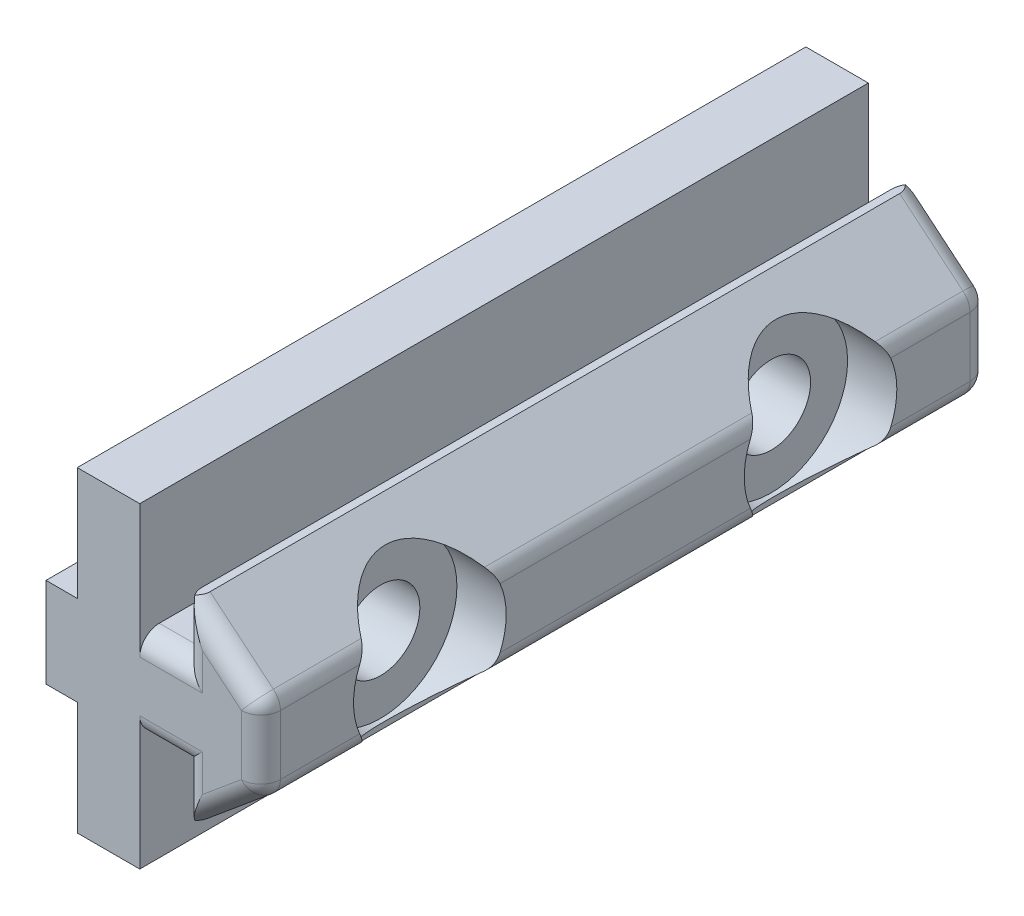
SolidWorks part; units mm, degrees
ref_plane "Front Plane" through (0, 0, 0) normal (0, 0, 1) x (1, 0, 0)
ref_plane "Top Plane" through (0, 0, 0) normal (0, 1, 0) x (1, 0, 0)
ref_plane "Right Plane" through (0, 0, 0) normal (1, 0, 0) x (0, 0, -1)
ref_plane "Plane1" through (0, 0, 23.6855) normal (0, 0, 1) x (1, 0, 0)
sketch "Sketch1" plane through (0, 0, 23.6855) normal (0, 0, 1) x (1, 0, 0)
  line L0 (3.302, 6.35) -> (-4.064, 6.35)
  line L1 (-4.064, 6.35) -> (-4.064, -6.35)
  line L2 (-4.064, -6.35) -> (3.302, -6.35)
  line L3 (3.302, -6.35) -> (7.874, -2.54)
  line L4 (7.874, -2.54) -> (7.874, 2.54)
  line L5 (7.874, 2.54) -> (3.302, 6.35)
extrude "Boss-Extrude1" add sketch "Sketch1" against normal blind 47.371
sketch "Sketch2" plane through (0, 0, 23.6855) normal (0, 0, 1) x (1, 0, 0)
  line L0 (-4.064, 6.35) -> (-4.064, 2.921)
  line L1 (-4.064, 2.921) -> (2.794, 2.921)
  line L2 (2.794, 2.921) -> (2.794, 6.35)
  line L3 (2.794, 6.35) -> (-4.064, 6.35)
extrude "Cut-Extrude1" cut sketch "Sketch2" against normal through all
sketch "Sketch3" plane through (0, 2.921, 0) normal (0, 1, 0) x (-1, 0, 0)
  line L0 (4.064, -23.6855) -> (0, -23.6855)
  line L1 (0, -23.6855) -> (0, 23.6855)
  line L2 (0, 23.6855) -> (4.064, 23.6855)
  line L3 (4.064, 23.6855) -> (4.064, -23.6855)
extrude "Boss-Extrude2" add sketch "Sketch3" along normal blind 7.366
sketch "Sketch4" plane through (0, 0, 23.6855) normal (0, 0, 1) x (1, 0, 0)
  line L0 (-4.064, -6.35) -> (2.794, -6.35)
  line L1 (2.794, -6.35) -> (2.794, -2.921)
  line L2 (2.794, -2.921) -> (-4.064, -2.921)
  line L3 (-4.064, -2.921) -> (-4.064, -6.35)
extrude "Cut-Extrude2" cut sketch "Sketch4" against normal through all
sketch "Sketch5" plane through (0, -2.921, 0) normal (0, -1, 0) x (1, 0, 0)
  line L0 (0, -23.6855) -> (-4.064, -23.6855)
  line L1 (-4.064, -23.6855) -> (-4.064, 23.6855)
  line L2 (-4.064, 23.6855) -> (0, 23.6855)
  line L3 (0, 23.6855) -> (0, -23.6855)
extrude "Boss-Extrude3" add sketch "Sketch5" along normal blind 7.366
hole_wizard "#3 Clearance Hole1" positions "Sketch7" profile "Sketch6" hole size "#3" standard "ANSI Inch"
sketch "Sketch7" plane through (-4.064, 0, 0) normal (-1, 0, 0) x (0, 0, 1)
  point P0 (12.7, 0)
  point P1 (-12.7, 0)
sketch "Sketch6" plane through (-4.064, 0, 12.7) normal (0, 1, 0) x (0, 0, 1)
  line L0 (0, 0) -> (0, 11.938)
  line L1 (0, 11.938) -> (1.3843, 11.938)
  line L2 (1.3843, 11.938) -> (1.3843, 0)
  line L5 (1.3843, 0) -> (0, 0)
  line L11 (0, -6.35) -> (0, 107.95) construction
  dimension "Thru Hole Dia." = 2.7686
  dimension "Thru Hole Depth" = 11.938
sketch "Sketch9" plane through (0, 0, 23.6855) normal (0, 0, 1) x (1, 0, 0)
  line L0 (-4.064, 10.287) -> (-4.064, -10.287) construction
  line L1 (-4.064, 2.921) -> (-6.096, 2.921)
  line L2 (-4.064, 2.921) -> (-4.064, -2.921)
  line L3 (-4.064, -2.921) -> (-6.096, -2.921)
  line L4 (-6.096, 2.921) -> (-6.096, -2.921)
  line L8 (0, 2.921) -> (2.794, 2.921) construction
  line L9 (2.794, -2.921) -> (0, -2.921) construction
  dimension "D1" = 2.032
  dimension "D2" = 5.842
extrude "Boss-Extrude4" add sketch "Sketch9" against normal through all
sketch "Sketch10" plane through (-4.064, 0, 0) normal (1, 0, 0) x (0, 0, -1)
  line L0 (-12.7, 1.3843) -> (-12.7, -1.3843) construction
  circle A0 centre (-12.7, 0) radius 1.3843 construction
  circle A1 centre (-12.7, 0) radius 1.3843 construction
  circle A2 centre (-12.7, 0) radius 1.3843
extrude "Cut-Extrude3" cut sketch "Sketch10" against normal blind 2.54
sketch "Sketch11" plane through (-4.064, 0, 0) normal (1, 0, 0) x (0, 0, -1)
  line L0 (12.7, 1.3843) -> (12.7, -1.3843) construction
  circle A0 centre (12.7, 0) radius 1.3843 construction
  circle A1 centre (12.7, 0) radius 1.3843 construction
  circle A2 centre (12.7, 0) radius 1.3843
extrude "Cut-Extrude4" [suppressed] cut sketch "Sketch11" against normal through all
sketch "Sketch12" plane through (7.874, 0, 0) normal (1, 0, 0) x (0, 0, -1)
  line L0 (-12.7, 1.3843) -> (-12.7, -1.3843) construction
  line L1 (12.7, 1.3843) -> (12.7, -1.3843) construction
  circle A0 centre (-12.7, 0) radius 1.3843 construction
  circle A1 centre (12.7, 0) radius 1.3843 construction
  point P5 (-12.7, 0)
  point P11 (12.7, 0)
hole_wizard "CBORE for #10 Button Head Cap Screw1" positions "Sketch13" profile "Sketch14" counterbore size "#10" standard "ANSI Inch" end condition through all
sketch "Sketch13" plane through (7.874, 0, 0) normal (1, 0, 0) x (0, 0, -1)
  point P0 (-12.7, 0)
  point P3 (12.7, 0)
sketch "Sketch14" plane through (7.874, 0, 12.7) normal (0, 1, 0) x (0, 0, -1)
  line L0 (0, 0) -> (0, 13.97)
  line L1 (0, 13.97) -> (2.5527, 13.97)
  line L3 (2.5527, 13.97) -> (2.5527, 3.2004)
  line L4 (2.5527, 3.2004) -> (4.9606, 3.2004)
  line L5 (4.9606, 3.2004) -> (4.9606, 0)
  line L7 (4.9606, 0) -> (0, 0)
  line L11 (0, -6.35) -> (0, 107.95) construction
  dimension "Thru Hole Dia." = 5.1054
  dimension "Thru Hole Depth" = 13.97
  dimension "C'Bore Dia." = 9.9212
  dimension "C'Bore Depth" = 3.2004
fillet "Fillet1" radius 1.27 6 edges at (7.874, -2.54, 20.3233) (7.874, -2.54, -20.3233) (7.874, -2.54, 0) (7.874, 2.54, 20.3233) (7.874, 2.54, 0) (7.874, 2.54, -20.3233)
fillet "Fillet3" radius 1.27 9 edges at (5.3595, -4.6354, -23.6855) (7.7541, -2.4838, -23.6855) (5.3595, 4.6354, -23.6855) (7.7541, 2.4838, -23.6855) (1.397, -2.921, -23.6855) (1.397, 2.921, -23.6855) (2.794, 4.6355, -23.6855) (2.794, -4.6355, -23.6855) (7.874, 0, -23.6855)
fillet "Fillet5" radius 1.27 9 edges at (5.3595, -4.6354, 23.6855) (7.7541, -2.4838, 23.6855) (5.3595, 4.6354, 23.6855) (7.7541, 2.4838, 23.6855) (2.794, 4.6355, 23.6855) (1.397, 2.921, 23.6855) (1.397, -2.921, 23.6855) (2.794, -4.6355, 23.6855) (7.874, 0, 23.6855)
